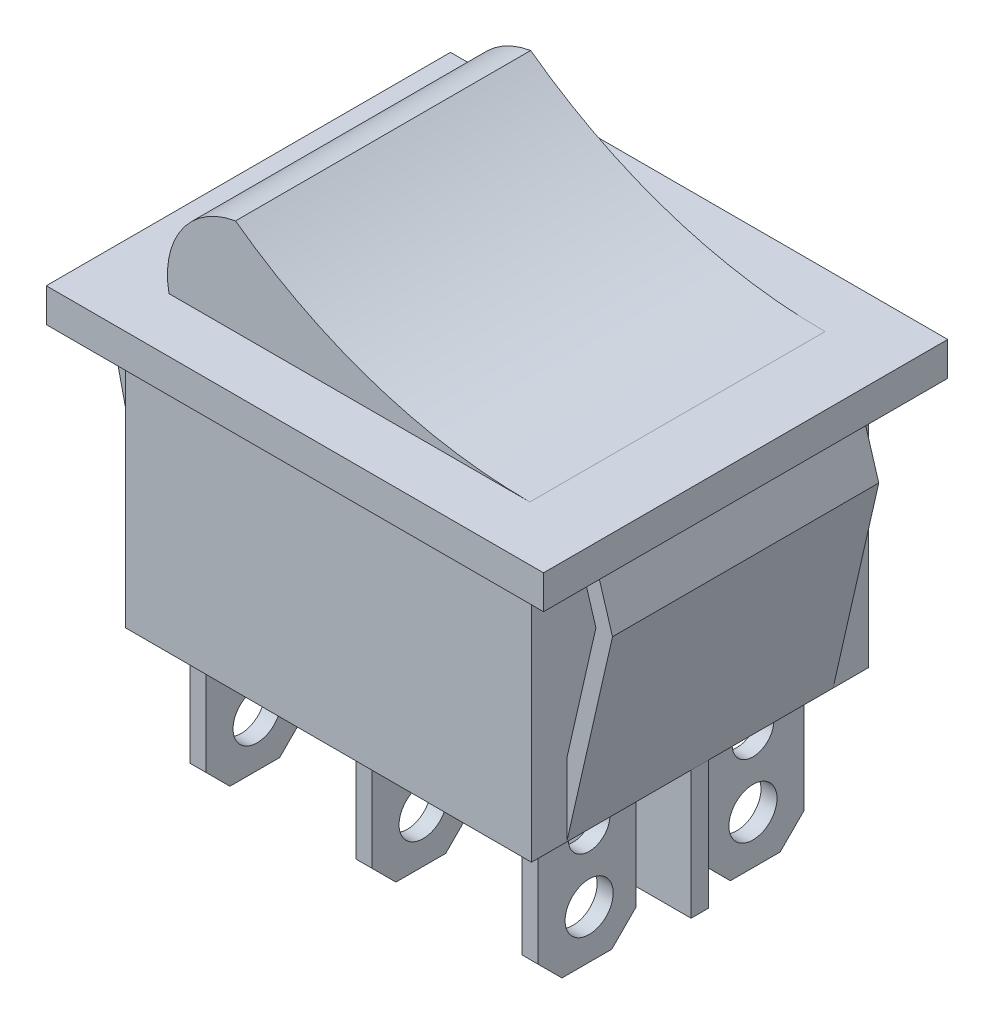
SolidWorks part; units mm, degrees
material "PEI"
ref_plane "前视基准面" through (0, 0, 0) normal (0, 0, 1) x (1, 0, 0)
ref_plane "上视基准面" through (0, 0, 0) normal (0, 1, 0) x (1, 0, 0)
ref_plane "右视基准面" through (0, 0, 0) normal (1, 0, 0) x (0, 0, -1)
other "Configuration Table"
sketch "草图1" plane through (0, 0, 0) normal (0, 0, 1) x (1, 0, 0)
  line L1 (0, 0) -> (25.3, 0)
  line L2 (0, 0) -> (0, 16)
  line L3 (0, 16) -> (25.3, 16)
  line L4 (25.3, 0) -> (25.3, 16)
  dimension "D1" = 25.3
  dimension "D2" = 16
extrude "凸台-拉伸1" add sketch "草图1" along normal blind 10.5 and the other way blind 10.5
sketch "草图2" plane through (0, 0, 0) normal (0, 0, 1) x (1, 0, 0)
  line L0 (25.3, 16) -> (0, 16) construction
  line L1 (-2.85, 18.1) -> (28.15, 18.1)
  line L2 (-2.85, 18.1) -> (-2.85, 16)
  line L3 (-2.85, 16) -> (28.15, 16)
  line L4 (28.15, 18.1) -> (28.15, 16)
  line L5 (12.65, 0) -> (12.65, 16) construction
  line L6 (0, 0) -> (25.3, 0) construction
  dimension "D1" = 2.1
  dimension "D2" = 31
extrude "凸台-拉伸2" add sketch "草图2" along normal blind 12.6 and the other way blind 12.6
sketch "草图3" plane through (0, 0, 0) normal (0, 0, 1) x (1, 0, 0)
  line L2 (28.15, 18.1) -> (-2.85, 18.1) construction
  line L3 (1.4, 18.1) -> (23.9, 18.1)
  line L4 (0, 0) -> (25.3, 0) construction
  arc A0 (1.4, 18.1) -> (5.5484, 24.1) centre (6.3901, 19.0839) cw
  arc A1 (5.5484, 24.1) -> (23.9, 18.1) centre (23.9, 49.165) ccw
  point P9 (12.65, 0)
  point P10 (12.65, 18.1)
  dimension "D1" = 22.5
  dimension "D2" = 6
extrude "凸台-拉伸3" add sketch "草图3" along normal blind 9.2 and the other way blind 9.2
sketch "草图4" plane through (0, 0, 0) normal (0, 0, 1) x (1, 0, 0)
  line L0 (12.65, 0) -> (12.65, 16) construction
  line L1 (0, 0) -> (25.3, 0) construction
  line L2 (25.3, 16) -> (0, 16) construction
  line L3 (0, 0) -> (-2.85, 12.5)
  line L4 (-2.85, 12.5) -> (-1.85, 15.8)
  line L6 (28.15, 18.1) -> (-2.85, 18.1) construction
  line L7 (-2.85, 16) -> (28.15, 16) construction
  line L8 (-2.85, 18.1) -> (-2.85, 16) construction
  line L9 (0, 4.4985) -> (-1.8161, 12.4638)
  line L10 (-1.8161, 12.4638) -> (-0.893, 15.51)
  line L11 (-1.85, 15.8) -> (-0.8051, 15.8)
  line L12 (-0.8051, 15.8) -> (-0.893, 15.51)
  line L13 (0, 0) -> (0, 4.4985)
  line L14 (0.975, 0.2223) -> (-1.8161, 12.4638) construction
  line L15 (25.3, 0) -> (25.3, 4.4985)
  line L16 (27.15, 15.8) -> (26.1051, 15.8)
  line L17 (27.1161, 12.4638) -> (26.193, 15.51)
  line L18 (28.15, 12.5) -> (27.15, 15.8)
  line L19 (25.3, 0) -> (28.15, 12.5)
  line L20 (25.3, 4.4985) -> (27.1161, 12.4638)
  line L21 (26.193, 15.51) -> (26.1051, 15.8)
  dimension "D1" = 15.5
  dimension "D2" = 5.6
  dimension "D3" = 0.2
  dimension "D4" = 1
  dimension "D5" = 1
extrude "凸台-拉伸4" add sketch "草图4" along normal blind 8.3 and the other way blind 8.3
sketch "草图5" plane through (0, 0, 0) normal (0, -1, 0) x (1, 0, 0)
  line L0 (12.65, 10.5) -> (12.65, -10.5) construction
  line L1 (0, 10.5) -> (25.3, 10.5) construction
  line L2 (0, -10.5) -> (25.3, -10.5) construction
  line L3 (0, 0) -> (25.3, 0) construction
  line L4 (25.3, -8.3) -> (25.3, 8.3) construction
  line L5 (25.3, 10.5) -> (0, 10.5) construction
  line L6 (1.8, 10.5) -> (2.8, 10.5)
  line L7 (1.8, 10.5) -> (1.8, 0)
  line L8 (1.8, 0) -> (2.8, 0)
  line L9 (2.8, 10.5) -> (2.8, -10.5)
  line L10 (12.15, 10.5) -> (13.15, 10.5)
  line L11 (12.15, 10.5) -> (12.15, -10.5)
  line L12 (12.15, 0) -> (13.15, 0)
  line L13 (13.15, 10.5) -> (13.15, -10.5)
  line L14 (22.5, 10.5) -> (23.5, 10.5)
  line L15 (22.5, 10.5) -> (22.5, -10.5)
  line L16 (22.5, 0) -> (23.5, 0)
  line L17 (23.5, 10.5) -> (23.5, 0)
  line L18 (1.8, 8.3) -> (23.5, 8.3)
  line L19 (1.8, 2.2) -> (23.5, 2.2)
  line L20 (1.8, 5.25) -> (23.5, 5.25) construction
  line L21 (1.8, -5.25) -> (23.5, -5.25) construction
  line L22 (1.8, -2.2) -> (23.5, -2.2)
  line L23 (1.8, -8.3) -> (23.5, -8.3)
  line L24 (22.5, -10.5) -> (23.5, -10.5)
  line L25 (12.15, -10.5) -> (13.15, -10.5)
  line L26 (1.8, -10.5) -> (1.8, 0)
  line L27 (1.8, -10.5) -> (2.8, -10.5)
  line L28 (23.5, -10.5) -> (23.5, -0.2343)
  dimension "D1" = 1
  dimension "D2" = 21.7
  dimension "D3" = 6.1
extrude "凸台-拉伸5" add sketch "草图5" along normal blind 9 contours L23 L28 L22 L15 | L11 L23 L13 L22 | L26 L23 L9 L22 | L7 L19 L9 L18 | L11 L19 L13 L18 | L15 L19 L17 L18 region at (2.3, 0, 5.25) region at (12.65, 0, 5.25) region at (2.3, 0, -5.25) region at (23, 0, 5.25) region at (12.65, 0, -5.25) region at (23, 0, -5.25)
sketch "草图6" plane through (0, 0, 0) normal (0, -1, 0) x (1, 0, 0)
  line L0 (0, -8.3) -> (0, 8.3) construction
  line L1 (0, 0.55) -> (25.3, 0.55)
  line L2 (0, 0.55) -> (0, -0.55)
  line L3 (0, -0.55) -> (25.3, -0.55)
  line L4 (25.3, 0.55) -> (25.3, -0.55)
  line L5 (25.3, -8.3) -> (25.3, 8.3) construction
  point P8 (0, 0)
  dimension "D1" = 1.1
extrude "凸台-拉伸6" add sketch "草图6" along normal blind 8
sketch "草图7" plane through (23.5, 0, 0) normal (1, 0, 0) x (0, 0, -1)
  line L0 (-8.3, -9) -> (-2.2, -9) construction
  line L1 (-8.3, -7.5) -> (-6.8, -9)
  line L2 (-8.3, -9) -> (-8.3, 0) construction
  line L3 (-3.6976, -9) -> (-2.2, -7.5)
  line L4 (-2.2, -9) -> (-2.2, 0) construction
  line L5 (0, -8) -> (0, 0) construction
  line L6 (0.55, -8) -> (-0.55, -8) construction
  line L7 (3.6976, -9) -> (2.2, -7.5)
  line L8 (8.3, -7.5) -> (6.8, -9)
  line L9 (-8.3, -7.5) -> (-8.3, -9)
  line L10 (-8.3, -9) -> (8.3, -9)
  line L11 (8.3, -9) -> (8.3, -7.5)
  line L12 (2.2, -7.5) -> (2.2, -9)
  line L13 (2.2, -9) -> (-2.2, -9)
  line L14 (-2.2, -9) -> (-2.2, -7.5)
  circle A0 centre (-5.1066, -6) radius 1.5
  circle A1 centre (-5.1066, -1.7143) radius 1.3
  circle A2 centre (5.1066, -1.7143) radius 1.3
  circle A3 centre (5.1066, -6) radius 1.5
  line M4 (2.2, 0) -> (2.2, -9)
  line M5 (2.2, -9) -> (8.3, -9)
  line M6 (8.3, -9) -> (8.3, 0)
  dimension "D1" = 3
  dimension "D2" = 2.6
  dimension "D3" = 3
  dimension "D4" = 1.5
  dimension "D5" = 1.5
  dimension "D6" = 1.4976
extrude "切除-拉伸1" cut sketch "草图7" against normal through all and the other way through all contours A0 | A1 | L9 L10 L1 | L7 M5 M4 | L10 L14 L3 | L8 M6 M5 | A3 | A2 region at (23.5, -8.5, -7.8) region at (23.5, -8.5, -2.6992) region at (23.5, -8.5, 2.6992) region at (23.5, -8.5, 7.8) region at (23.5, -6, 5.1066) region at (23.5, -1.7143, 5.1066) region at (23.5, -1.7143, -5.1066) region at (23.5, -6, -5.1066)
